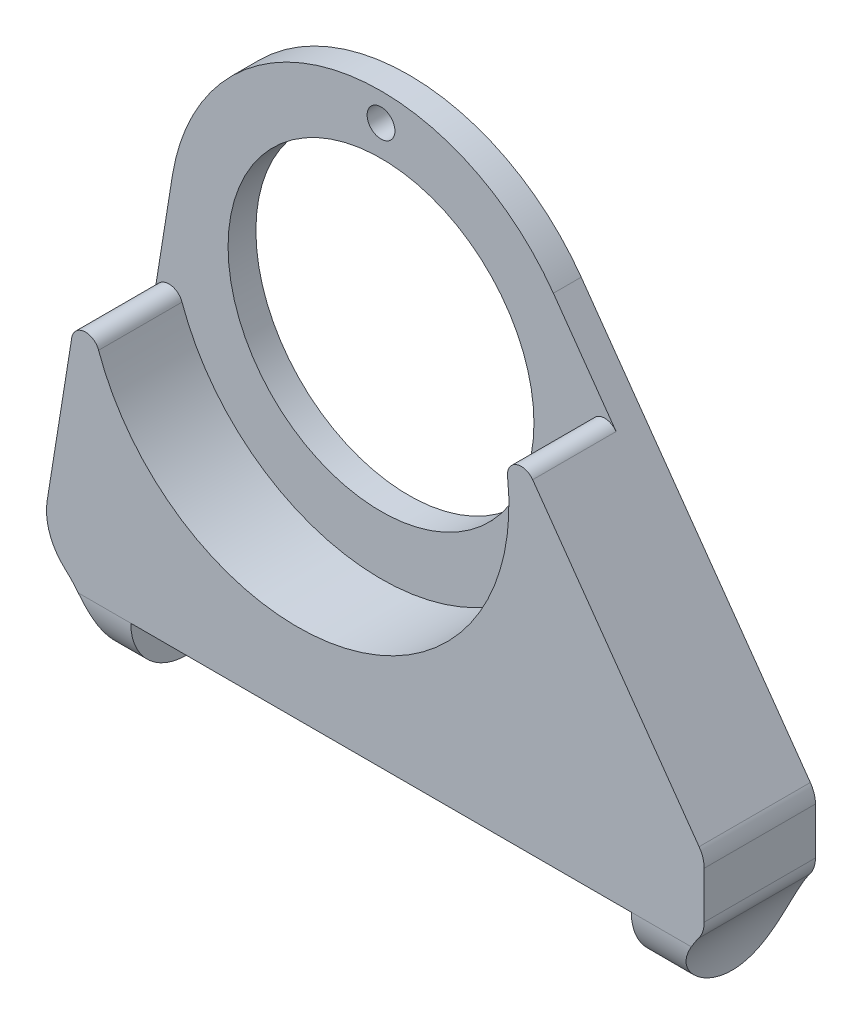
SolidWorks part; units mm, degrees
ref_plane "前视基准面" through (0, 0, 0) normal (0, 0, 1) x (1, 0, 0)
ref_plane "上视基准面" through (0, 0, 0) normal (0, 1, 0) x (1, 0, 0)
ref_plane "右视基准面" through (0, 0, 0) normal (1, 0, 0) x (0, 0, -1)
other "Configuration Table"
sketch "草图1" plane through (0, 0, 0) normal (0, 0, 1) x (1, 0, 0)
  circle A0 centre (0, 0) radius 38
  circle A1 centre (0, 0) radius 33 construction
  circle A2 centre (0, 33) radius 2.5
  circle A3 centre (0, 0) radius 27.5
  dimension "D1" = 76
  dimension "D2" = 66
  dimension "D3" = 5
  dimension "D4" = 55
extrude "凸台-拉伸1" add sketch "草图1" along normal blind 5
sketch "草图2" plane through (0, 0, 0) normal (0, 0, -1) x (-1, 0, 0)
  line L0 (-30.995, 21.9843) -> (-73.1164, -37.4014)
  line L1 (-73.1164, -37.4014) -> (-73.1164, -52.3924)
  line L2 (-73.1164, -52.3924) -> (46.8836, -52.3924)
  line L3 (46.8836, -52.3924) -> (37.521, 6.0146)
  circle A0 centre (0, 0) radius 38 construction
  arc A1 (-30.995, 21.9843) -> (37.521, 6.0146) centre (0, 0) ccw
  dimension "D1" = 120
extrude "凸台-拉伸2" add sketch "草图2" against normal blind 20
fillet "圆角2" radius 2.5 2 edges at (30.995, 21.9843, 12.5) (-37.521, 6.0146, 12.5)
fillet "圆角3" radius 10 1 edges at (-46.8836, -52.3924, 10)
fillet "圆角4" radius 5 2 edges at (73.1164, -52.3924, 10) (73.1164, -37.4014, 10)
sketch "草图3" plane through (0, -52.3924, 0) normal (0, -1, 0) x (1, 0, 0)
  line L0 (68.1164, 0) -> (68.1164, 20) construction
  line L1 (-35.153, 20) -> (68.1164, 20)
  line L2 (-35.153, 20) -> (-35.153, 10)
  line L3 (-35.153, 10) -> (68.1164, 10)
  line L4 (68.1164, 20) -> (68.1164, 10)
revolve "旋转1" add sketch "草图3" angle 180 about L3
fillet "圆角6" radius 20 2 edges at (68.1164, -52.3924, 10) (-35.153, -52.3924, 10)
ref_plane "基准面1" through (0, 0, 10) normal (0, 0, 1) x (1, 0, 0)
sketch "草图4" plane through (0, 0, 0) normal (1, 0, 0) x (0, 0, -1)
  line L0 (-10, -52.3924) -> (-10, 0) construction
  line L1 (-10, 0) -> (0, 0) construction
  circle A0 centre (-10, -52.3924) radius 10
  dimension "D1" = 20
extrude "切除-拉伸1" cut sketch "草图4" against normal blind 30 and the other way blind 60
